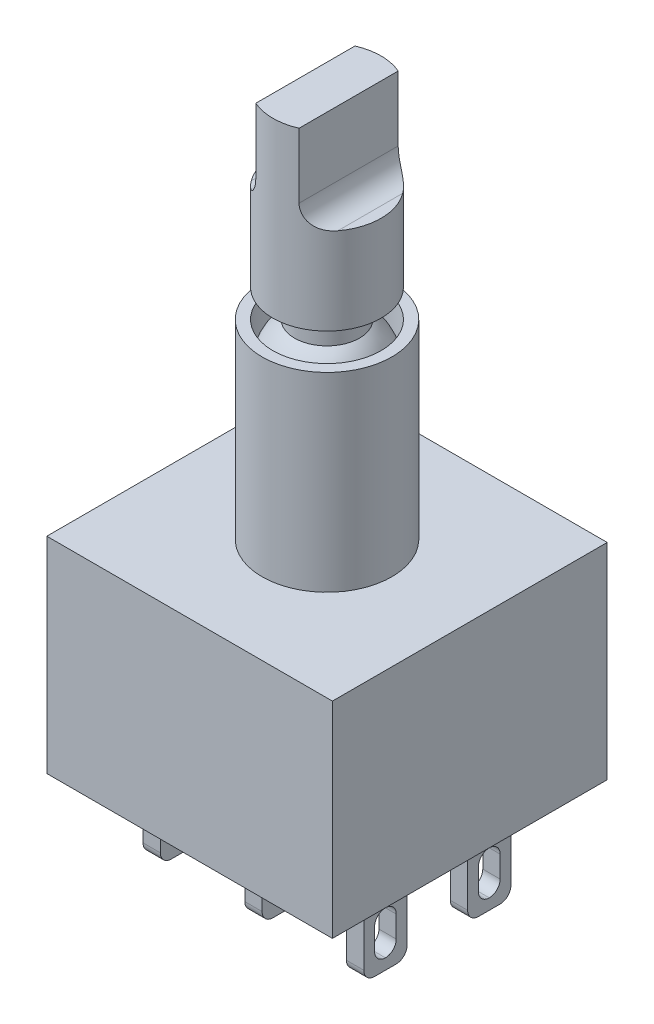
SolidWorks part; units mm, degrees
ref_plane "Спереди" through (0, 0, 0) normal (0, 0, 1) x (1, 0, 0)
ref_plane "Сверху" through (0, 0, 0) normal (0, 1, 0) x (1, 0, 0)
ref_plane "Справа" through (0, 0, 0) normal (1, 0, 0) x (0, 0, -1)
sketch "Sketch1" plane through (0, 0, 0) normal (0, 1, 0) x (1, 0, 0)
  line L1 (6.6, -6.35) -> (-6.6, -6.35)
  line L2 (6.6, -6.35) -> (6.6, 6.35)
  line L3 (6.6, 6.35) -> (-6.6, 6.35)
  line L4 (-6.6, -6.35) -> (-6.6, 6.35)
  line L5 (6.6, -6.35) -> (-6.6, 6.35) construction
  line L6 (6.6, 6.35) -> (-6.6, -6.35) construction
  point P0 (0, 0)
  dimension "D1" = 13.2
  dimension "D2" = 12.7
extrude "Boss-Extrude1" add sketch "Sketch1" along normal blind 9.5
sketch "Sketch2" plane through (0, 9.5, 0) normal (0, 1, 0) x (1, 0, 0)
  line L0 (-6.6, 6.35) -> (6.6, -6.35) construction
  circle A0 centre (0, 0) radius 3
  dimension "D1" = 6
extrude "Boss-Extrude2" add sketch "Sketch2" along normal blind 8.8
sketch "Sketch4" plane through (0, 18.3, 0) normal (0, 1, 0) x (1, 0, 0)
  circle A0 centre (0, 0) radius 2.5
  dimension "D1" = 5
extrude "Cut-Extrude1" cut sketch "Sketch4" against normal blind 2
sketch "Sketch5" plane through (0, 16.3, 0) normal (0, 1, 0) x (1, 0, 0)
  circle A0 centre (0, 0) radius 1.5
  dimension "D1" = 3
extrude "Boss-Extrude3" add sketch "Sketch5" along normal blind 5
sketch "Sketch3" plane through (0, 16.3, 0) normal (0, 1, 0) x (1, 0, 0)
  line L0 (0, -3) -> (0, 3) construction
  line L1 (0, -2.5) -> (0, 2.5)
  circle A0 centre (0, 0) radius 3 construction
  arc A1 (0, -2.5) -> (0, 2.5) centre (0, 0) cw
  point P7 (0, 0)
  dimension "D1" = 5
revolve "Revolve2" add sketch "Sketch3" angle 180 about L0
fillet "Fillet1" radius 1 1 edges at (0, 21.3, 1.5)
sketch "Sketch6" plane through (0, 0, 0) normal (0, -1, 0) x (1, 0, 0)
  line L0 (-4.7, 6.35) -> (-4.7, -6.35) construction
  line L1 (-6.6, 6.35) -> (6.6, 6.35) construction
  line L2 (6.6, -6.35) -> (-6.6, -6.35) construction
  line L3 (0, 6.35) -> (0, -6.35) construction
  line L4 (4.7, 6.35) -> (4.7, -6.35) construction
  line L6 (-6.6, 2.4) -> (6.6, 2.4) construction
  line L7 (-4.3, 1.4) -> (-5.1, 1.4)
  line L8 (-4.3, 1.4) -> (-4.3, 3.4)
  line L9 (-4.3, 3.4) -> (-5.1, 3.4)
  line L10 (-5.1, 1.4) -> (-5.1, 3.4)
  line L11 (-4.3, 1.4) -> (-5.1, 3.4) construction
  line L12 (-4.3, 3.4) -> (-5.1, 1.4) construction
  line L13 (-6.6, -6.35) -> (-6.6, 6.35) construction
  line L14 (6.6, 6.35) -> (6.6, -6.35) construction
  line L15 (-6.6, -2.4) -> (6.6, -2.4) construction
  line L16 (-6.6, 0) -> (6.6, 0) construction
  line L17 (-4.3, -3.4) -> (-5.1, -3.4)
  line L18 (-4.3, -3.4) -> (-4.3, -1.4)
  line L19 (-4.3, -1.4) -> (-5.1, -1.4)
  line L20 (-5.1, -3.4) -> (-5.1, -1.4)
  line L21 (-4.3, -3.4) -> (-5.1, -1.4) construction
  line L22 (-4.3, -1.4) -> (-5.1, -3.4) construction
  line L23 (0.4, -3.4) -> (-0.4, -3.4)
  line L24 (0.4, -3.4) -> (0.4, -1.4)
  line L25 (0.4, -1.4) -> (-0.4, -1.4)
  line L26 (-0.4, -3.4) -> (-0.4, -1.4)
  line L27 (0.4, -3.4) -> (-0.4, -1.4) construction
  line L28 (0.4, -1.4) -> (-0.4, -3.4) construction
  line L29 (0.4, 1.4) -> (-0.4, 1.4)
  line L30 (0.4, 1.4) -> (0.4, 3.4)
  line L31 (0.4, 3.4) -> (-0.4, 3.4)
  line L32 (-0.4, 1.4) -> (-0.4, 3.4)
  line L33 (0.4, 1.4) -> (-0.4, 3.4) construction
  line L34 (0.4, 3.4) -> (-0.4, 1.4) construction
  line L35 (5.1, 1.4) -> (4.3, 1.4)
  line L36 (5.1, 1.4) -> (5.1, 3.4)
  line L37 (5.1, 3.4) -> (4.3, 3.4)
  line L38 (4.3, 1.4) -> (4.3, 3.4)
  line L39 (5.1, 1.4) -> (4.3, 3.4) construction
  line L40 (5.1, 3.4) -> (4.3, 1.4) construction
  line L41 (5.1, -3.4) -> (4.3, -3.4)
  line L42 (5.1, -3.4) -> (5.1, -1.4)
  line L43 (5.1, -1.4) -> (4.3, -1.4)
  line L44 (4.3, -3.4) -> (4.3, -1.4)
  line L45 (5.1, -3.4) -> (4.3, -1.4) construction
  line L46 (5.1, -1.4) -> (4.3, -3.4) construction
  point P10 (0, 0)
  point P11 (-4.7, 2.4)
  point P27 (-4.7, -2.4)
  point P32 (0, -2.4)
  point P37 (0, 2.4)
  point P42 (4.7, 2.4)
  point P47 (4.7, -2.4)
  dimension "D1" = 4.7
  dimension "D2" = 4.7
  dimension "D3" = 2
  dimension "D4" = 0.8
  dimension "D5" = 4.8
  dimension "D6" = 2.4
extrude "Boss-Extrude4" add sketch "Sketch6" along normal blind 4
sketch "Sketch7" plane through (-5.1, 0, 0) normal (-1, 0, 0) x (0, 0, 1)
  line L0 (-2.4, -4) -> (-2.4, 0) construction
  line L1 (-1.4, -4) -> (-3.4, -4) construction
  line L2 (-1.4, 0) -> (-3.4, 0) construction
  line L3 (2.4, -4) -> (2.4, 0) construction
  line L6 (3.4, -4) -> (1.4, -4) construction
  line L7 (3.4, 0) -> (1.4, 0) construction
  line L8 (-3.4, -2.5) -> (3.4, -2.5) construction
  line L9 (-1.9, -3.5) -> (-2.9, -3.5)
  line L10 (-1.9, -3.5) -> (-1.9, -1.5)
  line L11 (-1.9, -1.5) -> (-2.9, -1.5)
  line L12 (-2.9, -3.5) -> (-2.9, -1.5)
  line L13 (-1.9, -3.5) -> (-2.9, -1.5) construction
  line L14 (-1.9, -1.5) -> (-2.9, -3.5) construction
  line L15 (2.9, -3.5) -> (1.9, -3.5)
  line L16 (2.9, -3.5) -> (2.9, -1.5)
  line L17 (2.9, -1.5) -> (1.9, -1.5)
  line L18 (1.9, -3.5) -> (1.9, -1.5)
  line L19 (2.9, -3.5) -> (1.9, -1.5) construction
  line L20 (2.9, -1.5) -> (1.9, -3.5) construction
  line L21 (-3.4, -4) -> (-3.4, 0) construction
  line L22 (3.4, -4) -> (3.4, 0) construction
  point P12 (-2.4, -2.5)
  point P17 (2.4, -2.5)
  dimension "D1" = 0.5
  dimension "D2" = 2
  dimension "D3" = 1
extrude "Cut-Extrude2" cut sketch "Sketch7" against normal through all
fillet "Fillet2" radius 0.5 36 edges at (4.7, -3.5, 2.9) (4.7, -3.5, 1.9) (4.7, -3.5, -1.9) (4.7, -3.5, -2.9) (4.7, -1.5, -1.9) (4.7, -1.5, 2.9) (4.7, -1.5, 1.9) (4.7, -1.5, -2.9) (0, -1.5, 1.9) (0, -1.5, 2.9) (0, -3.5, 2.9) (0, -3.5, 1.9) (0, -3.5, -1.9) (0, -3.5, -2.9) (0, -1.5, -2.9) (0, -1.5, -1.9) (-4.7, -3.5, 2.9) (-4.7, -1.5, 2.9) (-4.7, -3.5, 1.9) (-4.7, -1.5, 1.9) (-4.7, -1.5, -1.9) (-4.7, -1.5, -2.9) (-4.7, -3.5, -1.9) (-4.7, -3.5, -2.9) (0, -4, -1.4) (0, -4, -3.4) (4.7, -4, -1.4) (4.7, -4, -3.4) (4.7, -4, 1.4) (4.7, -4, 3.4) (0, -4, 3.4) (0, -4, 1.4) (-4.7, -4, 3.4) (-4.7, -4, 1.4) (-4.7, -4, -1.4) (-4.7, -4, -3.4)
sketch "Sketch8" plane through (0, 18.3, 0) normal (0, 1, 0) x (1, 0, 0)
  circle A0 centre (0, 0) radius 2.5
  dimension "D1" = 5
extrude "Boss-Extrude5" add sketch "Sketch8" along normal blind 4 from offset 1.3
sketch "Sketch9" plane through (0, 23.6, 0) normal (0, 1, 0) x (1, 0, 0)
  line L0 (0, -2.5) -> (0, 2.5) construction
  line L1 (-1, -2.2913) -> (-1, 2.2913)
  line L2 (1, 2.2913) -> (1, -2.2913)
  circle A0 centre (0, 0) radius 2.5 construction
  arc A1 (-1, -2.2913) -> (1, -2.2913) centre (0, 0) ccw
  arc A2 (-1, 2.2913) -> (1, 2.2913) centre (0, 0) cw
  dimension "D1" = 2
  dimension "D2" = 1
extrude "Boss-Extrude6" add sketch "Sketch9" along normal blind 4
fillet "Fillet3" radius 1 2 edges at (-1, 23.6, 0) (1, 23.6, 0)
